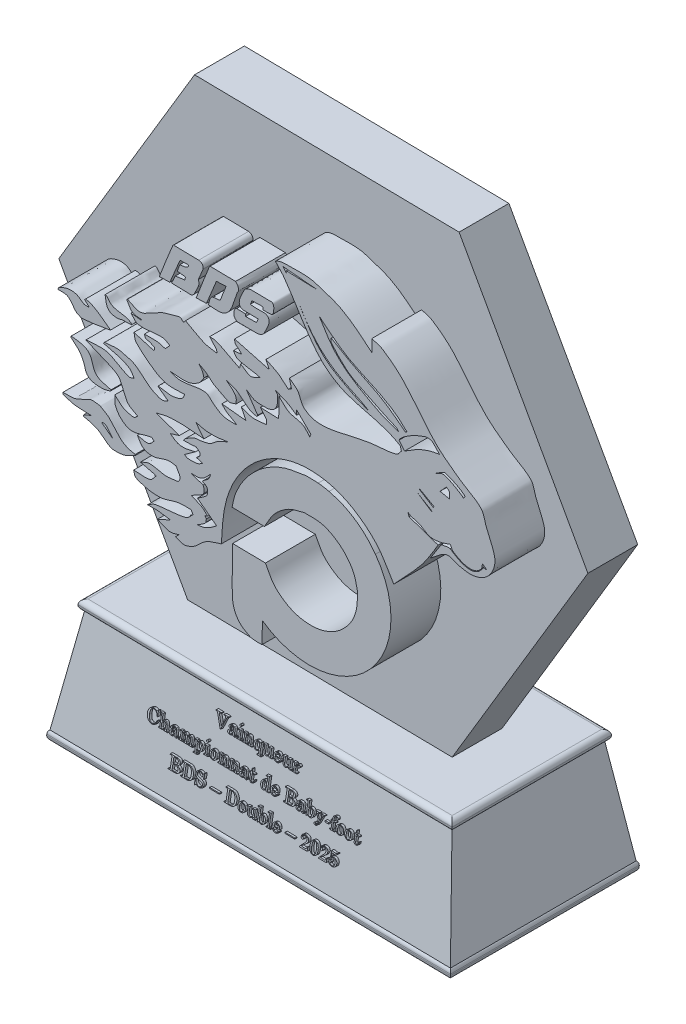
SolidWorks part; units mm, degrees
ref_plane "Plan de face" through (0, 0, 0) normal (0, 0, 1) x (1, 0, 0)
ref_plane "Plan de dessus" through (0, 0, 0) normal (0, 1, 0) x (1, 0, 0)
ref_plane "Plan de droite" through (0, 0, 0) normal (1, 0, 0) x (0, 0, -1)
sketch "Esquisse3" plane through (0, 0, 0) normal (0, 0, 1) x (1, 0, 0)
  line L0 (336.1667, 1024) -> (1680.8333, 1024) construction
  line L1 (1302, 1687) -> (1302, 1736)
  line L2 (1537, 1090) -> (1581, 1159)
  line L3 (1445.599, 1206.4377) -> (1452, 1191)
  line L4 (1452, 1191) -> (1568, 1151)
  line L5 (514, 653) -> (528, 667)
  line L6 (441, 677) -> (494, 701)
  line L7 (584, 764) -> (577, 778)
  line L8 (437, 826) -> (373, 842)
  line L9 (484, 1110) -> (443, 1141)
  line L10 (347, 1280) -> (428, 1256)
  line L11 (428, 1256) -> (430, 1269)
  line L12 (473, 1286) -> (491, 1306)
  line L13 (335, 1341) -> (376, 1337)
  line L14 (376, 1337) -> (378, 1339)
  line L15 (318, 1380) -> (321, 1382)
  line L16 (546, 1414) -> (554, 1424)
  line L17 (771, 1367) -> (775, 1384)
  line L18 (746, 1416) -> (780, 1420)
  line L19 (751, 1459) -> (890, 1422)
  line L20 (890, 1422) -> (877, 1451)
  line L21 (967, 1392) -> (980, 1399)
  line L22 (980, 1399) -> (971, 1433)
  line L23 (945, 1808) -> (1083, 1796)
  line L24 (1083, 1796) -> (959, 1800)
  line L25 (959, 1800) -> (958, 1794)
  line L26 (958, 1794) -> (960, 1791)
  line L27 (960, 1791) -> (945, 1808)
  line L28 (1444, 1481) -> (1437, 1478)
  line L29 (1433, 1410) -> (1411, 1437)
  line L30 (1677, 1373) -> (1670, 1365)
  line L31 (1613, 1334) -> (1576, 1342)
  line L32 (1601, 1369) -> (1576, 1342)
  line L33 (1000, 1318) -> (999, 1338)
  line L34 (999, 1338) -> (1057, 1281)
  line L35 (1057, 1281) -> (1053, 1269)
  line L36 (930, 1348) -> (928, 1270)
  line L37 (928, 1270) -> (855, 1273)
  line L38 (778, 1236) -> (797, 1198)
  line L39 (840, 1234) -> (844, 1240)
  line L40 (844, 1240) -> (799, 1306)
  line L41 (1654, 1326) -> (1658, 1324)
  line L42 (1658, 1324) -> (1654, 1325)
  line L43 (1654, 1326) -> (1654, 1325)
  line L44 (1551, 1277) -> (1494, 1309)
  line L45 (1551, 1277) -> (1549, 1272)
  line L46 (1549, 1272) -> (1493, 1307)
  line L47 (1493, 1307) -> (1494, 1309)
  line L48 (1483, 1293) -> (1544, 1256)
  line L49 (1542, 1254) -> (1544, 1256)
  line L50 (1542, 1254) -> (1483, 1293)
  line L51 (1746, 1175) -> (1763, 1163)
  line L52 (1763, 1163) -> (1760, 1162)
  line L53 (1760, 1162) -> (1750.0098, 1163.665)
  line L55 (1743, 1157) -> (1746, 1175)
  line L56 (598, 970) -> (623, 963)
  line L57 (550, 957) -> (594, 988)
  line L58 (493, 1001) -> (529, 1012)
  line L59 (529, 1012) -> (437, 1044)
  line L60 (595, 1092) -> (628, 1050)
  line L61 (602, 831) -> (679, 773)
  line L62 (638, 777) -> (631, 785)
  line L63 (631, 785) -> (643, 789)
  line L64 (574, 905) -> (625, 888)
  line L65 (232, 1354) -> (231, 1353)
  line L66 (168, 1277) -> (149, 1295)
  line L67 (153, 1299) -> (149, 1295)
  line L68 (255, 1034) -> (253, 1029)
  line L69 (95, 1141) -> (94, 1136)
  line L70 (352, 858) -> (352, 854)
  line L71 (144, 891) -> (144, 887)
  line L72 (144, 891) -> (174, 905)
  line L73 (62, 923) -> (62, 929)
  line L74 (1234, 1501) -> (1241.5869, 1497.8498)
  line L75 (678, 1623) -> (717, 1625)
  line L76 (862.8036, 535.7693) -> (861, 451)
  line L77 (743, 744) -> (875, 742)
  line L78 (871, 867) -> (741, 869)
  line L79 (865, 1617) -> (864, 1628)
  line L80 (821, 1627) -> (864, 1628)
  line L81 (821, 1627) -> (814, 1611)
  line L82 (794, 1568) -> (795, 1559)
  line L83 (795, 1559) -> (839, 1560)
  line L84 (839, 1560) -> (846, 1576)
  line L85 (693, 1564) -> (717, 1625)
  line L86 (700, 1208) -> (797, 1198)
  line L87 (678, 1623) -> (638, 1526)
  line L88 (638, 1526) -> (597, 1525)
  line L89 (498, 1527) -> (513, 1559)
  line L90 (513, 1559) -> (551, 1564)
  line L91 (551, 1564) -> (554, 1576)
  line L92 (554, 1576) -> (521, 1580)
  line L93 (521, 1580) -> (531, 1607)
  line L94 (567, 1620) -> (565, 1624)
  line L95 (565, 1624) -> (532, 1623)
  line L96 (532, 1623) -> (491, 1526)
  line L97 (491, 1526) -> (449, 1525)
  line L98 (624.8796, 1638.9367) -> (605.4226, 1592.9044)
  line L99 (604.6984, 1566.7534) -> (589.7477, 1536.2154)
  line L100 (573.9653, 1525) -> (498, 1527)
  line L101 (264.0246, 866.4916) -> (217, 902)
  arc A0 (607, 1661) -> (624.8796, 1638.9367) centre (606.6207, 1642.4164) cw
  arc A1 (605.4226, 1592.9044) -> (604.6984, 1566.7534) centre (576.3678, 1580.6235) cw
  arc A2 (589.7477, 1536.2154) -> (573.9653, 1525) centre (571.5353, 1545.1319) cw
  arc A3 (862.8036, 535.7693) -> (1316.5669, 993.1753) centre (1052.5129, 801.3486) ccw
  arc A4 (1129.8066, 1118.4411) -> (1086.8314, 1125.9164) centre (1052.5129, 801.3486) ccw
  spline S0 degree 3 poles (915, 1811) (920.6667, 1813.6667) (925.9164, 1817.5129) (932, 1819) (941.1183, 1821.2289) (950.6154, 1822.1997) (960, 1822) (1000.4122, 1821.1402) (1042.9169, 1827.5488) (1081, 1814) (1113.09, 1802.5833) (1146.9207, 1794.9796) (1177, 1779) (1222.6884, 1754.728) (1262.8151, 1720.7801) (1302, 1687) knots 0 0 0 0 1 1 1 2 2 2 3 3 3 4 4 4 5 5 5 5
  spline S1 degree 3 poles (1302, 1736) (1317, 1730.3333) (1333.5756, 1727.7691) (1347, 1719) (1375.3732, 1700.4659) (1402.4901, 1679.4098) (1426, 1655) (1472.4253, 1606.7976) (1509.2053, 1549.8439) (1556, 1502) (1583.8463, 1473.5293) (1617.0572, 1450.7835) (1649, 1427) (1678.4402, 1405.0798) (1714.1626, 1391.0701) (1740, 1365) (1752.6359, 1352.2503) (1753.5167, 1331.7388) (1760, 1315) (1771.8506, 1284.4039) (1788.3447, 1255.1289) (1795, 1223) (1798.2706, 1207.2107) (1795.1053, 1189.924) (1789, 1175) (1782.6895, 1159.5742) (1772.3333, 1145) (1759, 1135) (1744.6396, 1124.2297) (1726.7988, 1117.3288) (1709, 1115) (1690.0565, 1112.5214) (1670.8107, 1117.6598) (1652, 1121) (1635.0445, 1124.0108) (1618.6273, 1138.4821) (1602, 1134) (1576.7377, 1127.1902) (1558.6667, 1104.6667) (1537, 1090) knots 0 0 0 0 1 1 1 2 2 2 3 3 3 4 4 4 5 5 5 6 6 6 7 7 7 8 8 8 9 9 9 10 10 10 11 11 11 12 12 12 13 13 13 13
  spline S2 degree 3 poles (1581, 1159) (1592.9734, 1159.921) (1605.2835, 1164.5242) (1617, 1162.6354) knots 0 0 0 0 0.921032 0.921032 0.921032 0.921032
  spline S3 degree 3 poles (1626.6587, 1159.5467) (1622.8097, 1165.1023) (1620.6123, 1172.2204) (1617, 1178) knots 2.277549 2.277549 2.277549 2.277549 3 3 3 3
  spline S4 degree 3 poles (1617, 1178) (1603, 1173.6667) (1589.4463, 1167.4664) (1575, 1165) (1561.8527, 1162.7553) (1547.9107, 1160.6528) (1535, 1164) (1519.9865, 1167.8924) (1508.1253, 1179.5944) (1494, 1186) (1479.3968, 1192.6224) (1461.6455, 1193.1408) (1449, 1203) (1447.7012, 1204.0126) (1446.5813, 1205.1696) (1445.599, 1206.4377) knots 0 0 0 0 1 1 1 2 2 2 3 3 3 4 4 4 4.153424 4.153424 4.153424 4.153424
  spline S5 degree 3 poles (1568, 1151) (1562.6667, 1142) (1557.7044, 1132.7695) (1552, 1124) (1535.3644, 1098.4259) (1520.3192, 1071.6124) (1501, 1048) (1466.1847, 1005.448) (1427, 966.6667) (1390, 926) knots 0 0 0 0 1 1 1 2 2 2 3 3 3 3
  spline S6 degree 3 poles (1390, 926) (1370, 957.3333) (1353.6926, 991.3567) (1330, 1020) (1308.6483, 1045.8133) (1283.3166, 1068.6086) (1256, 1088) (1228.8829, 1107.2498) (1199.2278, 1123.5669) (1168, 1135) (1137.6118, 1146.1257) (1105.2971, 1152.9709) (1073, 1155) (1040.9523, 1157.0135) (1008.2798, 1154.2583) (977, 1147) (947.2739, 1140.1022) (918.485, 1128.1581) (892, 1113) (864.9769, 1097.534) (839.9344, 1078.0981) (818, 1056) (794.8916, 1032.7191) (774.5075, 1006.3461) (758, 978) (741.238, 949.2167) (728.0873, 918.0447) (719, 886) (703.7834, 832.3415) (700.9314, 775.6973) (698, 720) knots 0 0 0 0 1 1 1 2 2 2 3 3 3 4 4 4 5 5 5 6 6 6 7 7 7 8 8 8 9 9 9 10 10 10 10
  spline S7 degree 3 poles (698, 720) (678, 712.6667) (656.4567, 708.6361) (638, 698) (616.6203, 685.6795) (602.0285, 663.1191) (580, 652) (548.5317, 636.116) (537.3019, 642.1258) (514, 653) knots 0 0 0 0 1 1 1 2 2 2 3 3 3 3
  spline S8 degree 3 poles (528, 667) (525.4489, 666.4898) (497.27, 654.9179) (484, 660) (469.6066, 665.5124) (455.3333, 671.3333) (441, 677) knots 0 0 0 0 1 1 1 2 2 2 2
  spline S9 degree 3 poles (494, 701) (477, 703.3333) (460.1099, 706.6982) (443, 708) (429.3727, 709.0369) (415.6667, 708) (402, 708) knots 0 0 0 0 1 1 1 2 2 2 2
  spline S10 degree 3 poles (402, 708) (412, 713.3333) (420.9098, 721.6652) (432, 724) (472.1351, 732.4495) (514.3355, 729.562) (554, 740) (566.3846, 743.2591) (574, 756) (584, 764) knots 0 0 0 0 1 1 1 2 2 2 3 3 3 3
  spline S11 degree 3 poles (577, 778) (560, 777.6667) (542.804, 779.5957) (526, 777) (501.5513, 773.2234) (478.6767, 760.7501) (454, 759) (430.9039, 757.362) (407.166, 760.3084) (385, 767) (348.0895, 778.1428) (350.2029, 779.9856) (346, 801) knots 0 0 0 0 1 1 1 2 2 2 3 3 3 4 4 4 4
  spline S12 degree 3 poles (346, 801) (367.6667, 801) (390.1074, 795.2603) (411, 801) (422.5936, 804.185) (428.3333, 817.6667) (437, 826) knots 0 0 0 0 1 1 1 2 2 2 2
  spline S13 degree 3 poles (373, 842) (385, 846.3333) (396.25, 854.5364) (409, 855) (435.1955, 855.9526) (460.8999, 842.5721) (487, 845) (500.0501, 846.214) (513, 848.3333) (526, 850) knots 0 0 0 0 1 1 1 2 2 2 3 3 3 3
  spline S14 degree 3 poles (526, 850) (528, 856.3333) (533.3025, 862.4874) (532, 869) (529.7195, 880.4027) (521.3333, 889.6667) (516, 900) knots 0 0 0 0 1 1 1 2 2 2 2
  spline S15 degree 3 poles (516, 900) (505.3333, 901) (494.6103, 904.4832) (484, 903) (463.1813, 900.0899) (443.9834, 888.259) (423, 887) (409.6035, 886.1962) (395.1111, 889.4731) (384, 897) (373.1244, 904.3673) (368.6667, 918.3333) (361, 929) knots 0 0 0 0 1 1 1 2 2 2 3 3 3 4 4 4 4
  spline S16 degree 3 poles (361, 929) (376, 927) (391.1443, 920.1176) (406, 923) (415.5122, 924.8457) (420.6667, 935.6667) (428, 942) knots 0 0 0 0 1 1 1 2 2 2 2
  spline S17 degree 3 poles (428, 942) (424, 944.6667) (420.7819, 950.4947) (416, 950) (390.5019, 947.3623) (366.6332, 933.2229) (341, 933) (326.6401, 932.8751) (312.2458, 940.0695) (301, 949) (288.6786, 958.7846) (279.0102, 972.4593) (273, 987) (268.2733, 998.4355) (271, 1011.6667) (270, 1024) knots 0 0 0 0 1 1 1 2 2 2 3 3 3 4 4 4 5 5 5 5
  spline S18 degree 3 poles (270, 1024) (283.6667, 1013.6667) (294.8981, 998.8552) (311, 993) (347.6119, 979.6866) (348.3963, 982.3963) (362, 996) knots 0 0 0 0 1 1 1 2 2 2 2
  spline S19 degree 3 poles (362, 996) (349.3333, 1004) (334.0691, 1008.9069) (324, 1020) (313.6798, 1031.3697) (310.3408, 1047.5133) (303, 1061) (296.0028, 1073.8554) (292.6952, 1090.1997) (281, 1099) (257.6507, 1116.5698) (228.5806, 1124.8608) (202, 1137) (186.2331, 1144.2006) (170, 1150.3333) (154, 1157) knots 0 0 0 0 1 1 1 2 2 2 3 3 3 4 4 4 5 5 5 5
  spline S20 degree 3 poles (154, 1157) (155.3333, 1157.3333) (156.6257, 1157.9838) (158, 1158) (184.9981, 1158.3176) (212.8154, 1164.5853) (239, 1158) (269.9392, 1150.2189) (294.8755, 1126.5021) (325, 1116) (332.348, 1113.4383) (340.3333, 1118.6667) (348, 1120) knots 0 0 0 0 1 1 1 2 2 2 3 3 3 4 4 4 4
  spline S21 degree 3 poles (348, 1120) (341.6667, 1128.6667) (337.8909, 1139.9855) (329, 1146) (298.4419, 1166.6716) (259.637, 1171.4544) (224, 1181) knots 0 0 0 0 1 1 1 2 2 2 2
  spline S22 degree 3 poles (224, 1181) (226, 1182.6667) (227.4051, 1185.7896) (230, 1186) (253.9215, 1187.9396) (279.1881, 1193.4577) (302, 1186) (318.0306, 1180.7592) (335.4753, 1178.5719) (350, 1170) (376.6403, 1154.2779) (396.4202, 1128.0088) (424, 1114) (459.6438, 1095.8952) (463.5958, 1099.7979) (484, 1110) knots 0 0 0 0 1 1 1 2 2 2 3 3 3 4 4 4 5 5 5 5
  spline S23 degree 3 poles (443, 1141) (448.6949, 1142.8983) (443.1637, 1141.6511) (450, 1141) (469.6483, 1139.1287) (489.5876, 1132.4345) (509, 1136) (542.4065, 1142.1359) (543.3635, 1148.1815) (551, 1166) knots 0 0 0 0 1 1 1 2 2 2 3 3 3 3
  spline S24 degree 3 poles (551, 1166) (526.3333, 1166.3333) (501.1599, 1162.0146) (477, 1167) (458.1643, 1170.8867) (440.8598, 1181.1209) (425, 1192) (400.2227, 1208.996) (375.9299, 1227.515) (356, 1250) (349.0749, 1257.813) (350, 1270) (347, 1280) knots 0 0 0 0 1 1 1 2 2 2 3 3 3 4 4 4 4
  spline S25 degree 3 poles (430, 1269) (388.8184, 1289.0628) (394.9727, 1274.0957) (389, 1295) knots 0 0 0 0 1 1 1 1
  spline S26 degree 3 poles (389, 1295) (407, 1294.6667) (425.0994, 1295.9179) (443, 1294) (453.2906, 1292.8974) (463, 1288.6667) (473, 1286) knots 0 0 0 0 1 1 1 2 2 2 2
  spline S27 degree 3 poles (491, 1306) (482, 1310.3333) (473.9581, 1318.2159) (464, 1319) (430.7546, 1321.6178) (396.8737, 1310.3936) (364, 1316) (351.4189, 1318.1456) (344.6667, 1332.6667) (335, 1341) knots 0 0 0 0 1 1 1 2 2 2 3 3 3 3
  spline S28 degree 3 poles (378, 1339) (365.6667, 1341.6667) (351.4183, 1339.8809) (341, 1347) (329.9297, 1354.5647) (325.6667, 1369) (318, 1380) knots 0 0 0 0 1 1 1 2 2 2 2
  spline S29 degree 3 poles (321, 1382) (337.6667, 1375.6667) (353.1715, 1362.8181) (371, 1363) (388.3324, 1363.1769) (403.2308, 1375.8044) (419, 1383) (437.5803, 1391.4784) (454.2051, 1404.9727) (474, 1410) (535.009, 1425.4944) (528.4316, 1431.5684) (546, 1414) knots 0 0 0 0 1 1 1 2 2 2 3 3 3 4 4 4 4
  spline S30 degree 3 poles (554, 1424) (579.3333, 1410.6667) (603.3907, 1394.5593) (630, 1384) (645.7983, 1377.7308) (663.3333, 1377.3333) (680, 1374) knots 0 0 0 0 1 1 1 2 2 2 2
  spline S31 degree 3 poles (680, 1374) (679.3333, 1378) (680.2674, 1382.638) (678, 1386) (670.338, 1397.3609) (660, 1406.6667) (651, 1417) knots 0 0 0 0 1 1 1 2 2 2 2
  spline S32 degree 3 poles (651, 1417) (660, 1416) (669.6412, 1417.4828) (678, 1414) (710.0621, 1400.6408) (740, 1382.6667) (771, 1367) knots 0 0 0 0 1 1 1 2 2 2 2
  spline S33 degree 3 poles (775, 1384) (791.3079, 1376.2006) (808.3586, 1355.94) (825, 1363) (834.7522, 1367.1373) (844.3333, 1371.6667) (854, 1376) knots 0 0 0 0 1 1 1 2 2 2 2
  spline S34 degree 3 poles (854, 1376) (846, 1378) (838.054, 1380.2299) (830, 1382) (807.7162, 1386.8975) (784.1489, 1387.4397) (763, 1396) (754.8896, 1399.2828) (751.6667, 1409.3333) (746, 1416) knots 0 0 0 0 1 1 1 2 2 2 3 3 3 3
  spline S35 degree 3 poles (780, 1420) (749.6731, 1451.41) (753.337, 1435.6296) (751, 1459) knots 0 0 0 0 1 1 1 1
  spline S36 degree 3 poles (877, 1451) (893.6667, 1442.3333) (911.2896, 1435.2991) (927, 1425) (941.4558, 1415.5234) (953.6667, 1403) (967, 1392) knots 0 0 0 0 1 1 1 2 2 2 2
  spline S37 degree 3 poles (971, 1433) (982, 1424) (995.2325, 1417.1862) (1004, 1406) (1014.9466, 1392.0336) (1015.9477, 1371.0219) (1029, 1359) (1042.717, 1346.3659) (1061.5274, 1338.5577) (1080, 1336) (1108.8188, 1332.0097) (1138.5521, 1336.904) (1167, 1343) (1206.3139, 1351.4244) (1245.3733, 1361.1971) (1285, 1368) (1323.1007, 1374.5409) (1362.6291, 1373.1077) (1400, 1383) (1409.5699, 1385.5332) (1414, 1397) (1421, 1404) knots 0 0 0 0 1 1 1 2 2 2 3 3 3 4 4 4 5 5 5 6 6 6 7 7 7 7
  spline S38 degree 3 poles (1421, 1404) (1418.3333, 1410) (1418.5514, 1418.4939) (1413, 1422) (1392.0534, 1435.2294) (1368.4815, 1444.1007) (1345, 1452) (1296.0045, 1468.4823) (1244.0544, 1475.9476) (1196, 1495) (1167.7816, 1506.1879) (1141.5168, 1522.8061) (1118, 1542) (1095.6955, 1560.2044) (1076.9818, 1582.7512) (1060, 1606) (1020.8468, 1659.6027) (988.3318, 1717.8068) (950, 1772) (939.9132, 1786.2607) (926.6667, 1798) (915, 1811) knots 0 0 0 0 1 1 1 2 2 2 3 3 3 4 4 4 5 5 5 6 6 6 7 7 7 7
  spline S39 degree 3 poles (1234, 1501) (1233.3071, 1501.2746) (1232.6555, 1501.6452) (1232, 1502) (1204.3218, 1516.9788) (1175.736, 1530.3978) (1149, 1547) (1118.5402, 1565.9145) (1091.9951, 1591.6844) (1070, 1620) (1033.5835, 1666.8811) (1004.352, 1718.9828) (974, 1770) knots 5 5 5 5 6 6 6 7 7 7 8 8 8 9 9 9 9
  spline S40 degree 3 poles (974, 1770) (1009.2632, 1712.8836) (1040.7926, 1651.7205) (1088, 1604) (1103.129, 1588.7065) (1119.6469, 1574.7141) (1137, 1562) (1153.4175, 1549.9713) (1171.1465, 1539.7712) (1189, 1530) (1220.5161, 1512.7513) (1254.8005, 1500.4619) (1285, 1481) (1298.4541, 1472.3296) (1262.1817, 1489.0571) (1241.5869, 1497.8498) knots 0 0 0 0 1 1 1 2 2 2 3 3 3 4 4 4 4.876532 4.876532 4.876532 4.876532
  spline S41 degree 3 poles (1091, 1708) (1133.0564, 1673.7942) (1174.7177, 1637.6494) (1223, 1613) (1284.8912, 1581.4029) (1352.3155, 1557.8776) (1407, 1515) (1420.1811, 1504.6649) (1431.6667, 1492.3333) (1444, 1481) knots 0 0 0 0 1 1 1 2 2 2 3 3 3 3
  spline S42 degree 3 poles (1437, 1478) (1402.4117, 1505.2291) (1367.5024, 1532.6613) (1329, 1554) (1294.7083, 1573.005) (1258.5431, 1588.4558) (1224, 1607) (1195.1856, 1622.4688) (1167.3333, 1639.6667) (1139, 1656) knots 0 0 0 0 1 1 1 2 2 2 3 3 3 3
  spline S43 degree 3 poles (1139, 1656) (1139.3333, 1650.6667) (1136.7754, 1644.2611) (1140, 1640) (1156.078, 1618.7541) (1175.1654, 1599.7898) (1195, 1582) (1207.6652, 1570.6405) (1221.9981, 1561.0243) (1237, 1553) (1279.4612, 1530.2882) (1323.6737, 1511.0145) (1367, 1490) (1406.2609, 1470.9573) (1395.2349, 1482.5182) (1409, 1466) knots 0 0 0 0 1 1 1 2 2 2 3 3 3 4 4 4 5 5 5 5
  spline S44 degree 3 poles (1409, 1466) (1382.5166, 1475.5954) (1354.8689, 1482.7719) (1330, 1496) (1264.0429, 1531.0836) (1201.8033, 1560.9883) (1152, 1618) (1128.157, 1645.2939) (1110.3276, 1677.3424) (1091, 1708) knots 0 0 0 0 1 1 1 2 2 2 3 3 3 3
  spline S45 degree 3 poles (1411, 1437) (1422.7965, 1460.5929) (1479.2149, 1489.3274) (1503, 1497) (1509.6241, 1499.1368) (1516.0477, 1502.6689) (1523, 1503) (1528.3377, 1503.2542) (1533.6929, 1502.6244) (1539, 1502) (1546.2224, 1501.1503) (1568.8037, 1474.1963) (1574, 1469) knots 0 0 0 0 1 1 1 2 2 2 3 3 3 4 4 4 4
  spline S46 degree 3 poles (1574, 1469) (1515.6013, 1461.3828) (1480.7028, 1441.8019) (1433, 1410) knots 0 0 0 0 1 1 1 1
  spline S47 degree 3 poles (1556, 1394) (1558.3701, 1396.3701) (1590.3583, 1416) (1594, 1416) (1607.1855, 1416) (1667.2767, 1387.5849) (1677, 1373) knots 0 0 0 0 1 1 1 2 2 2 2
  spline S48 degree 3 poles (1670, 1365) (1657.2666, 1377.7334) (1604.6796, 1406.1748) (1589, 1407) (1577.874, 1407.5856) (1564.0025, 1397.8273) (1556, 1394) knots 0 0 0 0 1 1 1 2 2 2 2
  spline S49 degree 3 poles (1601, 1369) (1604.5506, 1366.1595) (1613.803, 1362.3203) (1614, 1357) (1614.284, 1349.3313) (1613.3333, 1341.6667) (1613, 1334) knots 0 0 0 0 1 1 1 2 2 2 2
  spline S50 degree 3 poles (914, 1363) (932, 1355.3333) (950.665, 1349.0706) (968, 1340) (979.4691, 1333.9987) (989.3333, 1325.3333) (1000, 1318) knots 0 0 0 0 1 1 1 2 2 2 2
  spline S51 degree 3 poles (1053, 1269) (1043.6667, 1278.3333) (1036.6084, 1290.7178) (1025, 1297) (1007.4766, 1306.4832) (985.5551, 1305.5757) (968, 1315) (953.219, 1322.9351) (942.6667, 1337) (930, 1348) knots 0 0 0 0 1 1 1 2 2 2 3 3 3 3
  spline S52 degree 3 poles (855, 1273) (882.3131, 1233.6692) (882.4018, 1251.411) (878, 1225) knots 0 0 0 0 1 1 1 1
  spline S53 degree 3 poles (878, 1225) (860.3333, 1223.6667) (842.6107, 1219.0628) (825, 1221) (808.6534, 1222.7981) (793.6667, 1231) (778, 1236) knots 0 0 0 0 1 1 1 2 2 2 2
  spline S54 degree 3 poles (700, 1208) (706.3333, 1201.6667) (711.7033, 1194.1943) (719, 1189) (731.5298, 1180.0804) (745.6667, 1173.6667) (759, 1166) knots 0 0 0 0 1 1 1 2 2 2 2
  spline S55 degree 3 poles (759, 1166) (757, 1165.3333) (755.1067, 1163.922) (753, 1164) (736.9555, 1164.5942) (720.3884, 1163.4201) (705, 1168) (691.6848, 1171.9629) (680.5843, 1181.3316) (669, 1189) (656.8812, 1197.0223) (648.4052, 1213.0732) (634, 1215) (592.68, 1220.5269) (547.8534, 1195.8903) (509, 1211) (503.981, 1212.9518) (499, 1215) (494, 1217) knots 0 0 0 0 1 1 1 2 2 2 3 3 3 4 4 4 5 5 5 6 6 6 6
  spline S56 degree 3 poles (494, 1217) (517.3333, 1216.3333) (540.9428, 1211.3594) (564, 1215) (579.9136, 1217.5127) (595.0147, 1225.4639) (608, 1235) (617.0274, 1241.6295) (621.3333, 1253) (628, 1262) knots 0 0 0 0 1 1 1 2 2 2 3 3 3 3
  spline S57 degree 3 poles (628, 1262) (625.6667, 1269.3333) (624.5116, 1277.1523) (621, 1284) (617.7448, 1290.3476) (612.3333, 1295.3333) (608, 1301) knots 0 0 0 0 1 1 1 2 2 2 2
  spline S58 degree 3 poles (608, 1301) (617.3333, 1295.6667) (627.138, 1291.0844) (636, 1285) (649.5212, 1275.7168) (660.3578, 1262.3895) (675, 1255) (734.878, 1224.7812) (723.0011, 1223.8575) (757, 1236) knots 0 0 0 0 1 1 1 2 2 2 3 3 3 3
  spline S59 degree 3 poles (757, 1236) (756.6667, 1244.3333) (759.5511, 1253.4538) (756, 1261) (748.0708, 1277.8495) (730.7925, 1288.6881) (716, 1300) knots 0 0 0 0 1 1 1 2 2 2 2
  spline S60 degree 3 poles (716, 1300) (730, 1294.6667) (745.1306, 1291.6696) (758, 1284) (778.4448, 1271.8157) (794.6796, 1253.3905) (815, 1241) (822.3886, 1236.4947) (831.6667, 1236.3333) (840, 1234) knots 0 0 0 0 1 1 1 2 2 2 3 3 3 3
  spline S61 degree 3 poles (799, 1306) (810.3333, 1299.3333) (820.288, 1289.3606) (833, 1286) (850.1072, 1281.4774) (868.3163, 1283.6316) (886, 1283) (887.0534, 1282.9624) (888.0572, 1283.5286) (889, 1284) (896.7345, 1287.8672) (906.3175, 1289.4818) (912, 1296) (918.3862, 1303.3254) (922.4031, 1313.3001) (923, 1323) (924.841, 1352.9155) (924.4477, 1352.5523) (914, 1363) knots 0 0 0 0 1 1 1 2 2 2 3 3 3 4 4 4 5 5 5 6 6 6 6
  spline S62 degree 3 poles (595, 1092) (609.6667, 1088.6667) (624.0211, 1083.3617) (639, 1082) (675.9728, 1078.6388) (692.3078, 1083.4907) (725, 1088) knots 0 0 0 0 1 1 1 2 2 2 2
  spline S63 degree 3 poles (725, 1088) (711.5274, 1081.2637) (696.9722, 1076.6557) (684, 1069) (673.3204, 1062.6973) (664.9736, 1052.7756) (654, 1047) (645.6935, 1042.6282) (636.1763, 1040.9764) (627, 1039) (602.8772, 1033.8043) (599.6204, 1038.6814) (587, 1032) (576.3252, 1026.3486) (565.0499, 1021.6999) (555, 1015) (550.8769, 1012.2513) (548.3333, 1007.6667) (545, 1004) knots 0 0 0 0 1 1 1 2 2 2 3 3 3 4 4 4 5 5 5 6 6 6 6
  spline S64 degree 3 poles (545, 1004) (600.4214, 1002.0889) (592.1008, 1015.5116) (613, 992) knots 0 0 0 0 1 1 1 1
  spline S65 degree 3 poles (613, 992) (612.3333, 988.6667) (612.915, 984.8086) (611, 982) (607.6779, 977.1275) (602.3333, 974) (598, 970) knots 0 0 0 0 1 1 1 2 2 2 2
  spline S66 degree 3 poles (623, 963) (617.6667, 959.6667) (612.9666, 954.9889) (607, 953) (598.6813, 950.2271) (589.7671, 948.8346) (581, 949) (558.8759, 949.4174) (560.1362, 949.3979) (550, 957) knots 0 0 0 0 1 1 1 2 2 2 3 3 3 3
  spline S67 degree 3 poles (594, 988) (578, 985) (562.2776, 979.201) (546, 979) (520.046, 978.6796) (511.1814, 987.869) (493, 1001) knots 0 0 0 0 1 1 1 2 2 2 2
  spline S68 degree 3 poles (437, 1044) (438.3333, 1044.6667) (439.5424, 1045.6877) (441, 1046) (458.2591, 1049.6984) (475.4011, 1054.6462) (493, 1056) (519.5902, 1058.0454) (546.4778, 1057.7918) (573, 1055) (591.3078, 1053.0729) (609.6667, 1051.6667) (628, 1050) knots 0 0 0 0 1 1 1 2 2 2 3 3 3 4 4 4 4
  spline S69 degree 3 poles (655, 941) (652.6667, 934.6667) (652.1823, 927.2976) (648, 922) (641.8381, 914.1949) (632.3071, 909.745) (625, 903) (623.5718, 901.6817) (623, 899.6667) (622, 898) knots 0 0 0 0 1 1 1 2 2 2 3 3 3 3
  spline S70 degree 3 poles (622, 898) (627.7349, 895.1326) (635.2169, 894.1768) (639, 889) (644.2386, 881.8315) (644.3408, 863.1311) (637, 856) (626.7162, 846.01) (613.1955, 839.9564) (602, 831) knots 0 0 0 0 1 1 1 2 2 2 3 3 3 3
  spline S71 degree 3 poles (679, 773) (653.2815, 754.2956) (635.6045, 739) (603, 739) knots 0 0 0 0 1 1 1 1
  spline S72 degree 3 poles (603, 739) (613, 746) (624.7304, 751.0215) (633, 760) (637.0016, 764.3446) (636.3333, 771.3333) (638, 777) knots 0 0 0 0 1 1 1 2 2 2 2
  spline S73 degree 3 poles (643, 789) (635.3333, 795.6667) (628.6155, 803.6153) (620, 809) (606.7117, 817.3052) (591.5494, 822.1802) (577, 828) knots 0 0 0 0 1 1 1 2 2 2 2
  spline S74 degree 3 poles (577, 828) (616.4664, 852.9685) (638.0843, 848.747) (625, 888) knots 0 0 0 0 1 1 1 1
  spline S75 degree 3 poles (574, 905) (587.3333, 905.6667) (601.3163, 902.8352) (614, 907) (630.8684, 912.5389) (642.4457, 928.4457) (655, 941) knots 0 0 0 0 1 1 1 2 2 2 2
  spline S76 degree 3 poles (232, 1354) (242.4415, 1351.9117) (248.1212, 1335.3194) (258, 1330) (283.5429, 1316.2461) (317.1934, 1324.8066) (339, 1303) knots 0 0 0 0 1 1 1 2 2 2 2
  spline S77 degree 3 poles (339, 1303) (338.3333, 1302.3333) (337.9399, 1301.0742) (337, 1301) (325.0326, 1300.0552) (312.9871, 1300.648) (301, 1300) (296.7122, 1299.7682) (287.0907, 1296) (283, 1296) (239.2897, 1296) (236.3377, 1315.6359) (231, 1353) knots 0 0 0 0 1 1 1 2 2 2 3 3 3 4 4 4 4
  spline S78 degree 3 poles (42, 1277) (43, 1279.3333) (42.9398, 1282.5167) (45, 1284) (51.6537, 1288.7907) (59.2562, 1292.3065) (67, 1295) (74.7182, 1297.6846) (82.8298, 1299.8398) (91, 1300) (100.0965, 1300.1784) (109.5318, 1299.3268) (118, 1296) (128.5895, 1291.8398) (136.3646, 1282.0414) (147, 1278) (153.5509, 1275.5107) (161, 1277.3333) (168, 1277) knots 0 0 0 0 1 1 1 2 2 2 3 3 3 4 4 4 5 5 5 6 6 6 6
  spline S79 degree 3 poles (153, 1299) (192.7282, 1291.9891) (220.1759, 1262.8827) (253, 1241) knots 0 0 0 0 1 1 1 1
  spline S80 degree 3 poles (253, 1241) (252.3333, 1240.6667) (251.7352, 1240.1225) (251, 1240) (210.5395, 1233.2566) (176.8812, 1226.7192) (137, 1224) (136.2564, 1223.9493) (135.673, 1224.6795) (135, 1225) (128.6728, 1228.0129) (121.209, 1229.3119) (116, 1234) (104.2292, 1244.5937) (97.4114, 1260.1646) (85, 1270) (73.6184, 1279.0194) (56.5056, 1276.3093) (42, 1277) knots 0 0 0 0 1 1 1 2 2 2 3 3 3 4 4 4 5 5 5 6 6 6 6
  spline S81 degree 3 poles (95, 1141) (114.8476, 1138.9108) (147.1123, 1136.4433) (163, 1122) (187.4478, 1099.7747) (173.8492, 1057.8926) (219, 1044) (219.3388, 1043.8958) (245.2794, 1035.9441) (255, 1034) knots 0 0 0 0 1 1 1 2 2 2 3 3 3 3
  spline S82 degree 3 poles (253, 1029) (243.9623, 1025.9874) (234.6235, 1022.6637) (225, 1022) (203.027, 1020.4846) (168.7372, 1020.6485) (156, 1044) (151.1278, 1052.9324) (149.628, 1063.5673) (146, 1073) (142.3376, 1082.5223) (136.6973, 1092.4541) (131, 1101) (121.2159, 1115.6762) (106.0916, 1123.9084) (94, 1136) knots 0 0 0 0 1 1 1 2 2 2 3 3 3 4 4 4 5 5 5 5
  spline S83 degree 3 poles (62, 929) (77.3333, 929.3333) (92.6763, 929.3615) (108, 930) (108.7447, 930.031) (109.3133, 930.7101) (110, 931) (124.3148, 937.044) (138.77, 942.7588) (153, 949) (161.8999, 952.9034) (170.2844, 959.7741) (180, 960) (190.0472, 960.2337) (200.0277, 958.2465) (210, 957) (210.7396, 956.9075) (211.3659, 956.3917) (212, 956) (222.7019, 949.39) (234.3976, 944.1251) (244, 936) (256.2407, 925.6425) (265.9722, 912.6404) (277, 901) (283.9723, 893.6403) (289.9517, 885.1646) (298, 879) (305.8143, 873.0146) (314.8261, 868.5676) (324, 865) (332.9664, 861.5131) (342.6667, 860.3333) (352, 858) knots 0 0 0 0 1 1 1 2 2 2 3 3 3 4 4 4 5 5 5 6 6 6 7 7 7 8 8 8 9 9 9 10 10 10 11 11 11 11
  spline S84 degree 3 poles (352, 854) (338.6667, 847.6667) (326.0036, 839.6679) (312, 835) (301.7579, 831.586) (290.7946, 830.1799) (280, 830) (270.5732, 829.8429) (260.4327, 829.7836) (252, 834) (233.8035, 843.0982) (219.813, 859.1721) (202, 869) (184.2757, 878.7789) (163.6925, 882.3113) (144, 887) knots 0 0 0 0 1 1 1 2 2 2 3 3 3 4 4 4 5 5 5 5
  spline S85 degree 3 poles (174, 905) (144.9735, 907.7319) (114.3398, 903.8741) (87, 914) (78.6945, 917.0761) (70.3333, 920) (62, 923) knots 0 0 0 0 1 1 1 2 2 2 2
  spline S86 degree 3 poles (217, 902) (237.2594, 912.1297) (250.3229, 878.0008) (264.0246, 866.4916) knots 0 0 0 0 0.954263 0.954263 0.954263 0.954263
  spline S87 degree 3 poles (741, 869) (745.6667, 887.3333) (747.7541, 906.5247) (755, 924) (764.8836, 947.837) (777.0331, 970.9791) (792, 992) (806.9169, 1012.9507) (824.8476, 1031.8352) (844, 1049) (860.3907, 1063.6898) (878.7758, 1076.2821) (898, 1087) (916.6558, 1097.401) (936.5111, 1105.9645) (957, 1112) (979.7651, 1118.706) (1003.646, 1120.7794) (1027, 1125) (1031.3144, 1125.7797) (1035.6196, 1127.1844) (1040, 1127) (1063.1964, 1126.0233) (1077.3953, 1125.9069) (1086.8314, 1125.9164) knots 0 0 0 0 1 1 1 2 2 2 3 3 3 4 4 4 5 5 5 6 6 6 7 7 7 7.312652 7.312652 7.312652 7.312652
  spline S88 degree 3 poles (1129.8066, 1118.4411) (1149.3282, 1112.2707) (1169.4776, 1107.6732) (1188, 1099) (1210.21, 1088.6001) (1231.5798, 1075.9766) (1251, 1061) (1276.9315, 1041.002) (1298.6831, 1018.304) (1316.5669, 993.1753) knots 8.076053 8.076053 8.076053 8.076053 9 9 9 10 10 10 10.407544 10.407544 10.407544 10.407544
  spline S89 degree 3 poles (861, 451) (860.7904, 451.0102) (822.8237, 449.1685) (811, 456) (798.6701, 463.124) (785.1535, 469.0158) (775, 479) (764.7166, 489.112) (756.2735, 501.5765) (751, 515) (745.0476, 530.1515) (742.5683, 546.7311) (742, 563) (739.8935, 623.2975) (742.6667, 683.6667) (743, 744) knots 0 0 0 0 1 1 1 2 2 2 3 3 3 4 4 4 5 5 5 5
  spline S90 degree 3 poles (875, 742) (886.3333, 722.6667) (894.6188, 701.1873) (909, 684) (922.3654, 668.0268) (939.2502, 654.8959) (957, 644) (973.3018, 633.993) (991.3781, 626.3721) (1010, 622) (1030.1849, 617.2609) (1051.3145, 615.5856) (1072, 617) (1090.7946, 618.2851) (1109.6347, 622.6968) (1127, 630) (1145.7608, 637.8901) (1163.6526, 648.6329) (1179, 662) (1195.0596, 675.9874) (1208.9898, 692.77) (1220, 711) (1229.601, 726.8968) (1236.1194, 744.8388) (1240, 763) (1244.5408, 784.251) (1243.7239, 806.3068) (1245, 828) (1245.0619, 829.0523) (1244.2849, 829.9851) (1244, 831) (1238.9512, 848.9864) (1237.0946, 868.1632) (1229, 885) (1220.1849, 903.3353) (1207.9538, 920.1953) (1194, 935) (1180.3243, 949.5096) (1164.2355, 961.9753) (1147, 972) (1131.2153, 981.1809) (1113.9175, 988.4777) (1096, 992) (1074.3909, 996.248) (1052.0135, 994.3619) (1030, 995) (1028.9463, 995.0305) (1028.0082, 994.3076) (1027, 994) (1008.3412, 988.3075) (988.4483, 985.7242) (971, 977) (952.6309, 967.8155) (935.7836, 955.2556) (921, 941) (899.5706, 920.3359) (885.381, 893.0655) (871, 867) knots 0 0 0 0 1 1 1 2 2 2 3 3 3 4 4 4 5 5 5 6 6 6 7 7 7 8 8 8 9 9 9 10 10 10 11 11 11 12 12 12 13 13 13 14 14 14 15 15 15 16 16 16 17 17 17 18 18 18 19 19 19 19
  spline S91 degree 3 poles (846, 1576) (825.6667, 1576.3333) (805.3255, 1576.3443) (785, 1577) (784.5288, 1577.0152) (784.4216, 1577.7892) (784, 1578) (781.0636, 1579.4682) (777.3214, 1579.6786) (775, 1582) (763.606, 1593.394) (773.1825, 1614.365) (779, 1626) (782.4673, 1632.9346) (785.5327, 1640.0654) (789, 1647) (794.1673, 1657.3346) (809.3479, 1662.8816) (820, 1663) (846.0005, 1663.2889) (872.0062, 1662.6581) (898, 1662) (913.4911, 1661.6078) (908.2556, 1631.6817) (905, 1623) (904.1724, 1620.7931) (902.3379, 1618.2997) (900, 1618) (888.4233, 1616.5158) (876.6667, 1617.3333) (865, 1617) knots 0 0 0 0 1 1 1 2 2 2 3 3 3 4 4 4 5 5 5 6 6 6 7 7 7 8 8 8 9 9 9 10 10 10 10
  spline S92 degree 3 poles (814, 1611) (834.3961, 1607.6007) (855.3353, 1609.7251) (876, 1609) (876.4711, 1608.9835) (876.5784, 1608.2108) (877, 1608) (900.3349, 1596.3325) (886.7947, 1573.5894) (878, 1556) (871.5364, 1543.0728) (872.5797, 1541.8957) (866, 1534) (861.0143, 1528.0171) (851.4293, 1524.2346) (844, 1524) (816.3471, 1523.1268) (788.6647, 1523.6707) (761, 1524) (760.5286, 1524.0056) (760.4093, 1524.7661) (760, 1525) (745.7347, 1533.1516) (744.2607, 1553.1129) (755, 1566) (756.4315, 1567.7178) (758.7669, 1568.8855) (761, 1569) (771.9906, 1569.5636) (783, 1568.3333) (794, 1568) knots 0 0 0 0 1 1 1 2 2 2 3 3 3 4 4 4 5 5 5 6 6 6 7 7 7 8 8 8 9 9 9 10 10 10 10
  spline S93 degree 3 poles (597, 1525) (614.6667, 1570) (631.5443, 1615.3178) (650, 1660) (650.6363, 1661.5404) (652.3334, 1662.9841) (654, 1663) (687.6717, 1663.3207) (721.3333, 1661.6667) (755, 1661) knots 0 0 0 0 1 1 1 2 2 2 3 3 3 3
  spline S94 degree 3 poles (755, 1661) (758.3333, 1656.6667) (763.712, 1653.3132) (765, 1648) (769.3984, 1629.8564) (765.2762, 1633.7036) (762, 1626) (745.1615, 1586.4069) (740.6004, 1525.4277) (688, 1523) (673.999, 1522.3538) (660, 1524.3333) (646, 1525) knots 0 0 0 0 1 1 1 2 2 2 3 3 3 4 4 4 4
  spline S95 degree 3 poles (646, 1525) (649.1605, 1534.4815) (649.9589, 1557.3414) (665, 1561) (674.1208, 1563.2186) (683.6667, 1563) (693, 1564) knots 0 0 0 0 1 1 1 2 2 2 2
  spline S96 degree 3 poles (449, 1525) (467, 1570) (483.6751, 1615.5528) (503, 1660) (503.8916, 1662.0506) (506.764, 1662.9785) (509, 1663) (541.672, 1663.3142) (574.3333, 1661.6667) (607, 1661) knots 0 0 0 0 1 1 1 2 2 2 3 3 3 3
  spline S97 degree 3 poles (531, 1607) (548.3042, 1610.708) (556.4301, 1605.9067) (567, 1620) knots 0 0 0 0 1 1 1 1
  spline S98 degree 3 poles (1626.6587, 1159.5467) (1661.3206, 1136.2747) (1712.7818, 1114.6388) (1743, 1157) knots 0 0 0 0 1 1 1 1
  spline S99 degree 3 poles (1617, 1162.6354) (1656.216, 1134.436) (1715.0222, 1104.1743) (1750.0098, 1163.665) knots 0 0 0 0 1 1 1 1
  point P209 (862.8036, 535.7693)
  point P210 (1316.5669, 993.1753)
extrude "Boss.-Extru.1" add sketch "Esquisse3" along normal blind 200
sketch "Esquisse4" plane through (0, 0, 0) normal (0, 0, -1) x (-1, 0, 0)
  line L0 (-875, 742) -> (-743, 744) construction
  line L1 (-390.38, 2097.2194) -> (-1452.38, 2081.1285)
  line L2 (-1452.38, 2081.1285) -> (-1969.4449, 1153.364)
  line L3 (-1969.4449, 1153.364) -> (-1424.5097, 241.6905)
  line L4 (-1424.5097, 241.6905) -> (-362.5097, 257.7814)
  line L5 (-362.5097, 257.7814) -> (154.5551, 1185.5459)
  line L6 (154.5551, 1185.5459) -> (-390.38, 2097.2194)
  circle A0 centre (-907.4449, 1169.455) radius 919.8245 construction
  dimension "D1" = 1062
extrude "Boss.-Extru.2" add sketch "Esquisse4" along normal blind 200 separate body
sketch "Esquisse5" plane through (3.9881, 263.2136, 0) normal (-0.0151, -0.9999, 0) x (0.9999, -0.0151, 0)
  line L1 (158.5628, 200) -> (1620.6847, 200)
  line L2 (158.5628, 200) -> (158.5628, -400)
  line L3 (158.5628, -400) -> (1620.6847, -400)
  line L4 (1620.6847, 200) -> (1620.6847, -400)
  line L7 (1420.6847, 0) -> (358.5628, 0) construction
  line L8 (1420.6847, -200) -> (358.5628, -200) construction
  line L9 (1420.6847, -200) -> (1420.6847, 0) construction
  line L10 (358.5628, -200) -> (358.5628, 0) construction
  dimension "D1" = 200
  dimension "D2" = 200
  dimension "D3" = 200
  dimension "D4" = 200
extrude "Boss.-Extru.3" add sketch "Esquisse5" along normal blind 500 draft 9 draft outward yes
sketch "Esquisse11" plane through (3.9881, 263.2136, 0) normal (0.0151, 0.9999, 0) x (0.9999, -0.0151, 0)
  line L0 (158.5628, 400) -> (1620.6847, 400) construction
  line L1 (138.5628, 420) -> (1640.6847, 420)
  line L2 (138.5628, 420) -> (138.5628, -220)
  line L3 (138.5628, -220) -> (1640.6847, -220)
  line L4 (1640.6847, 420) -> (1640.6847, -220)
  line L5 (1620.6847, 400) -> (1620.6847, -200) construction
  line L6 (1620.6847, -200) -> (158.5628, -200) construction
  line L7 (158.5628, -200) -> (158.5628, 400) construction
  dimension "D1" = 20
  dimension "D2" = 20
  dimension "D3" = 20
  dimension "D4" = 20
extrude "Boss.-Extru.7" add sketch "Esquisse11" against normal blind 40
fillet "Congé1" radius 20 8 edges at (141.929, 221.119, -100) (142.535, 261.1144, -100) (892.9037, 209.7406, -420) (893.5097, 249.736, -420) (1644.4845, 238.3576, -100) (1643.8785, 198.3622, -100) (892.9037, 209.7406, 220) (893.5097, 249.736, 220)
sketch "Esquisse15" plane through (-3.5868, -236.729, 0) normal (-0.0151, -0.9999, 0) x (0.9999, -0.0151, 0)
  line L4 (79.3706, 279.1922) -> (79.3706, -479.1922)
  line L5 (79.3706, -479.1922) -> (1699.8769, -479.1922)
  line L6 (1699.8769, -479.1922) -> (1699.8769, 279.1922)
  line L7 (1699.8769, 279.1922) -> (79.3706, 279.1922)
  line L8 (79.3706, 279.1922) -> (79.3706, -479.1922)
  line L9 (79.3706, -479.1922) -> (1699.8769, -479.1922)
  line L10 (1699.8769, -479.1922) -> (1699.8769, 279.1922)
  line L11 (1699.8769, 279.1922) -> (79.3706, 279.1922)
  dimension "D1" = 0
extrude "Boss.-Extru.8" add sketch "Esquisse15" against normal blind 40
fillet "Congé5" radius 20 8 edges at (75.7747, -237.9315, -100) (76.3806, -197.9361, -100) (885.9348, -250.2066, 279.1922) (886.5408, -210.2112, 279.1922) (1696.095, -262.4818, -100) (885.9348, -250.2066, -479.1922) (886.5408, -210.2112, -479.1922) (1696.701, -222.4864, -100)
sketch "Esquisse18" plane through (0.5657, 37.3394, 235.7791) normal (0.0024, 0.1564, 0.9877) x (1, -0.0004, -0.0023)
  line L0 (155.0267, 185.9184) -> (118.5883, -26.1778) construction
  line L1 (82.1498, -238.2739) -> (155.0267, 185.9184) construction
  line L2 (118.5883, -26.1778) -> (1659.7298, -49.2409) construction
  line L3 (1689.8054, -262.3325) -> (1629.6543, 163.8507) construction
  line L4 (1659.7298, -49.2409) -> (1629.6543, 163.8507) construction
  line L5 (1644.692, 57.3049) -> (136.8075, 79.8703) construction
  text T0 "Vainqueur  \r\nChampionnat de Baby-foot  \r\nBDS – Double – 2025" font "Century Schoolbook" height 50
extrude "Boss.-Extru.11" add sketch "Esquisse18" along normal blind 10 separate body
